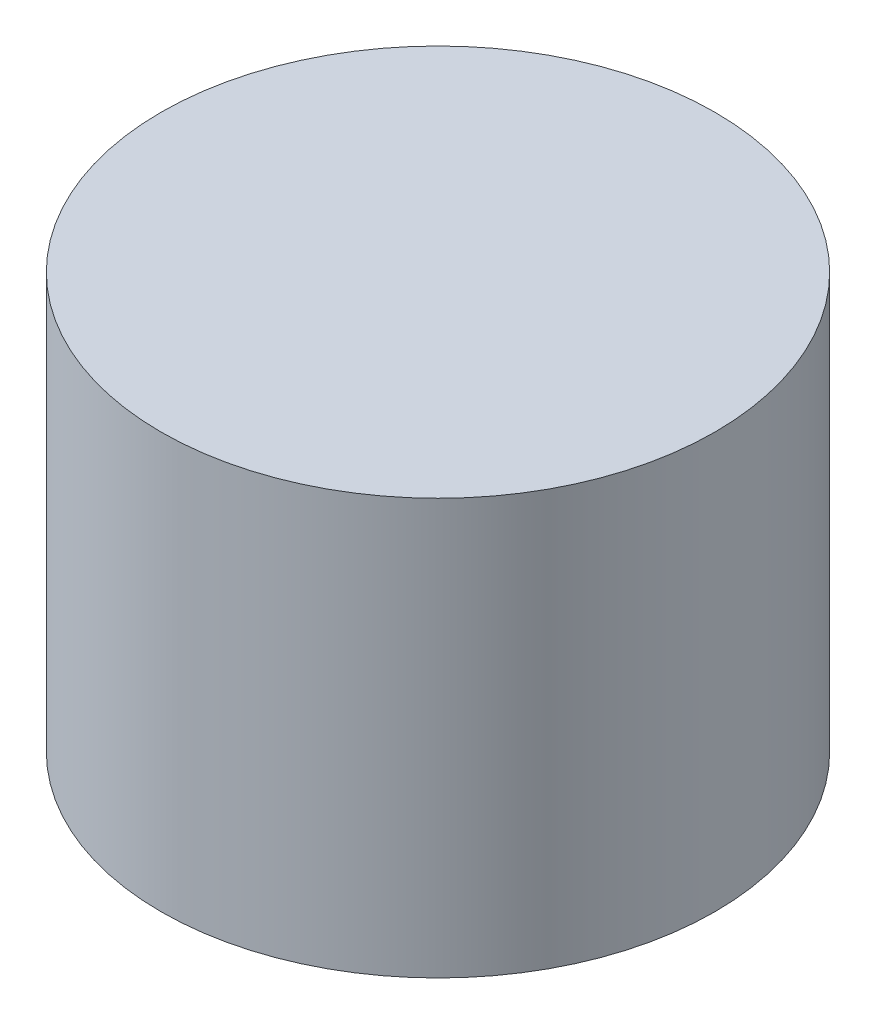
SolidWorks part; units mm, degrees
ref_plane "Front Plane" through (0, 0, 0) normal (0, 0, 1) x (1, 0, 0)
ref_plane "Top Plane" through (0, 0, 0) normal (0, 1, 0) x (1, 0, 0)
ref_plane "Right Plane" through (0, 0, 0) normal (1, 0, 0) x (0, 0, -1)
sketch "Sketch1" plane through (0, 0, 0) normal (0, 1, 0) x (1, 0, 0)
  circle A0 centre (0, 0) radius 1
  dimension "D1" = 2
extrude "Boss-Extrude1" add sketch "Sketch1" along normal blind 1.5
